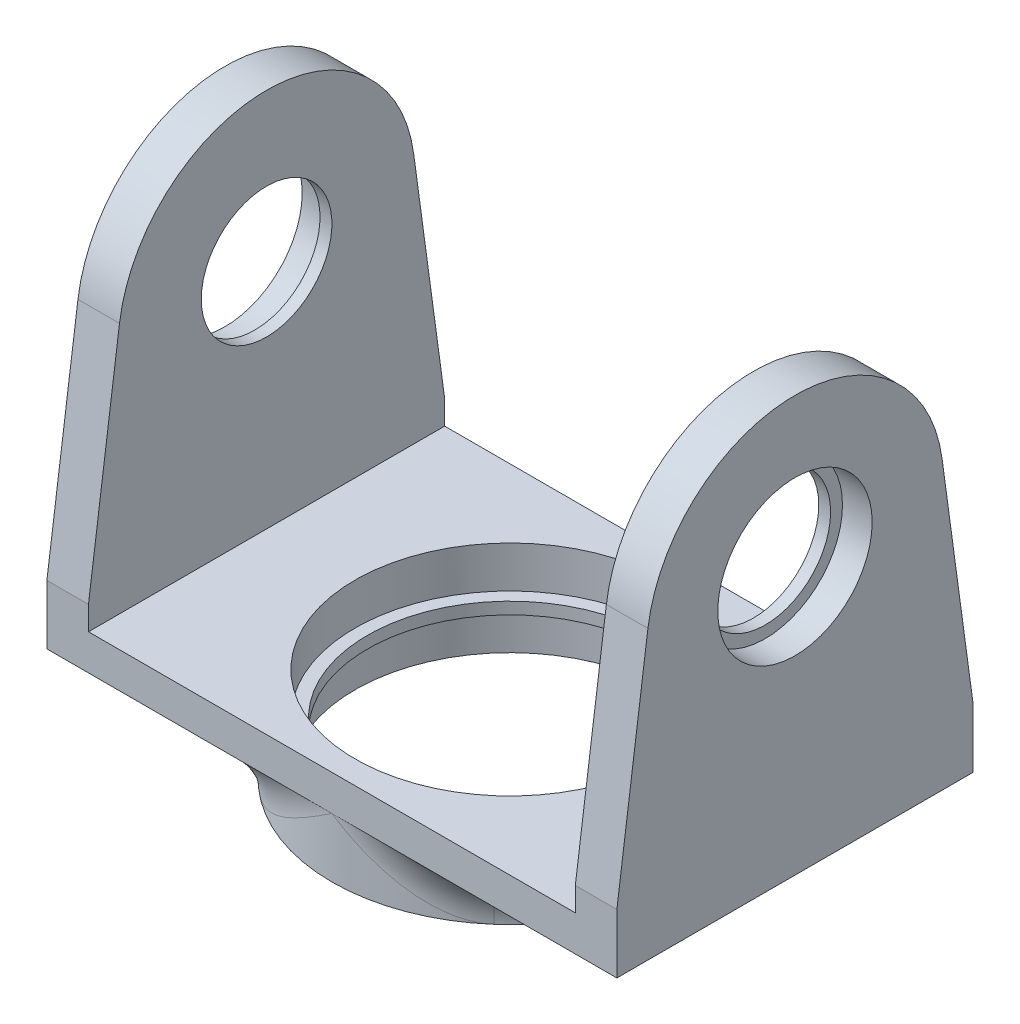
SolidWorks part; units mm, degrees
ref_plane "Front Plane" through (0, 0, 0) normal (0, 0, 1) x (1, 0, 0)
ref_plane "Top Plane" through (0, 0, 0) normal (0, 1, 0) x (1, 0, 0)
ref_plane "Right Plane" through (0, 0, 0) normal (1, 0, 0) x (0, 0, -1)
sketch "Sketch1" plane through (0, 0, 0) normal (0, 0, 1) x (1, 0, 0)
  line L1 (0, 0) -> (96, 0)
  line L3 (7, 16) -> (89, 16)
  line L6 (0, 0) -> (0, 80)
  line L7 (0, 80) -> (7, 80)
  line L8 (7, 16) -> (7, 80)
  line L10 (96, 0) -> (96, 80)
  line L11 (96, 80) -> (89, 80)
  line L12 (89, 16) -> (89, 80)
  dimension "D1" = 7
  dimension "D2" = 16
  dimension "D3" = 80
  dimension "D4" = 96
extrude "Boss-Extrude1" add sketch "Sketch1" along normal blind 60
sketch "Sketch2" plane through (96, 0, 0) normal (1, 0, 0) x (0, 0, -1)
  line L0 (-60, 80) -> (0, 80) construction
  line L1 (-60, 20) -> (-54.7711, 58.3752)
  line L2 (-60, 0) -> (-60, 80) construction
  line L3 (-60, 0) -> (0, 0) construction
  line L4 (-5.2289, 58.3752) -> (0, 20)
  line L5 (0, 0) -> (0, 80) construction
  line L6 (-60, 20) -> (0, 20)
  line L7 (-60, 20) -> (-60, 80)
  line L8 (-60, 80) -> (0, 80)
  line L9 (0, 80) -> (0, 20)
  circle A0 centre (-30, 55) radius 13
  arc A1 (-5.2289, 58.3752) -> (-54.7711, 58.3752) centre (-30, 55) ccw
  point P4 (-30, 80)
  line M2 (0, 0) -> (0, 80)
  line M3 (0, 80) -> (-60, 80)
  line M4 (-60, 80) -> (-60, 0)
  dimension "D1" = 26
  dimension "D2" = 25
  dimension "D3" = 20
extrude "Cut-Extrude1" cut sketch "Sketch2" against normal through all contours A1 L8 L1 M4 | A1 L4 M2 M3 | A0 region at (96, 64.3268, 54.5563) region at (96, 64.3268, 5.4437) region at (96, 55, 30)
sketch "Sketch3" plane through (0, 0, 0) normal (0, -1, 0) x (-1, 0, 0)
  line L0 (0, -60) -> (0, 0) construction
  line L1 (0, -60) -> (-96, -60) construction
  circle A0 centre (-48, -30) radius 26.1
  point P4 (0, -30)
  point P7 (-48, -60)
  dimension "D1" = 52.2
extrude "Cut-Extrude2" cut sketch "Sketch3" against normal blind 35
sketch "Sketch4" plane through (0, 0, 0) normal (-1, 0, 0) x (0, 0, 1)
  circle A0 centre (30, 55) radius 13
  circle A1 centre (30, 55) radius 11
  dimension "D1" = 22
extrude "Boss-Extrude2" add sketch "Sketch4" along normal blind 2 from surface starting at face at (7, 55, 43)
extrude "Boss-Extrude3" add sketch "Sketch4<2>" against normal blind 2 from surface starting at face at (89, 55, 17)
sketch "Sketch4<2>" plane through (0, 0, 0) normal (-1, 0, 0) x (0, 0, 1) same geometry as "Sketch4"
sketch "Sketch5" plane through (0, 16, 0) normal (0, 1, 0) x (1, 0, 0)
  circle A0 centre (48, -30) radius 26.1
  circle A1 centre (48, -30) radius 24
  dimension "D1" = 48
  dimension "D2" = 52.2
extrude "Boss-Extrude4" add sketch "Sketch5" against normal blind 2 from offset 7 offset against normal yes
sketch "Sketch6" plane through (0, 0, 0) normal (0, -1, 0) x (-1, 0, 0)
  line L1 (0, -60) -> (-96, -60)
  line L2 (0, -60) -> (0, 0)
  line L3 (0, 0) -> (-96, 0)
  line L4 (-96, -60) -> (-96, 0)
  circle A0 centre (-48, -30) radius 30
  line M7 (0, 0) -> (-96, 0)
  line M8 (-96, 0) -> (-96, -60)
  line M9 (-96, -60) -> (0, -60)
  line M10 (0, -60) -> (0, 0)
extrude "Cut-Extrude3" cut sketch "Sketch6" against normal blind 10 contours A0 L1 M10 M7 | A0 L3 M8 M9 region at (13.1363, 0, 30) region at (82.8637, 0, 30)
fillet "Fillet1" radius 10 2 edges at (18, 10, 30) (78, 10, 30)
